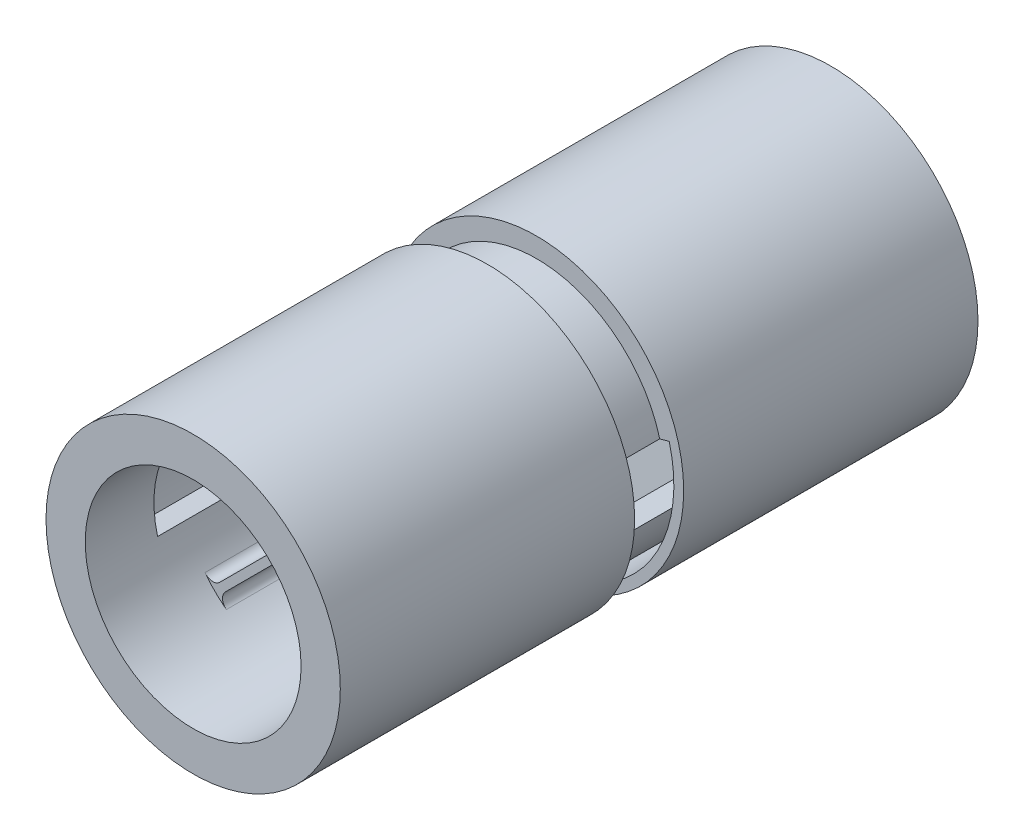
SolidWorks part; units mm, degrees
material "AISI 316 Stainless Steel Sheet (SS)"
ref_plane "Front Plane" through (0, 0, 0) normal (0, 0, 1) x (1, 0, 0)
ref_plane "Top Plane" through (0, 0, 0) normal (0, 1, 0) x (1, 0, 0)
ref_plane "Right Plane" through (0, 0, 0) normal (1, 0, 0) x (0, 0, -1)
sketch "Sketch1" plane through (0, 0, 0) normal (0, 0, 1) x (1, 0, 0)
  line L0 (-10.6252, -2.847) -> (-13.523, -3.6235)
  line L1 (0, 0) -> (-15, 0) construction
  line L2 (0, 0) -> (0, -15) construction
  line L3 (10.6252, -2.847) -> (13.523, -3.6235)
  line L4 (-13.523, -3.6235) -> (0, 0) construction
  line L5 (13.523, -3.6235) -> (0, 0) construction
  circle A0 centre (0, 0) radius 15
  arc A1 (13.523, -3.6235) -> (-13.523, -3.6235) centre (0, 0) ccw
  arc A2 (-10.6252, -2.847) -> (10.6252, -2.847) centre (0, 0) ccw
  dimension "D1" = 30
  dimension "D2" = 28
  dimension "D3" = 22
  dimension "D4" = 15
extrude "Boss-Extrude1" add sketch "Sketch1" along normal blind 45
sketch "Sketch2" plane through (0, 0, 0) normal (0, 0, -1) x (-1, 0, 0)
  circle A0 centre (0, 0) radius 15
  circle A1 centre (0, 0) radius 15 construction
  circle A2 centre (0, 0) radius 13
  dimension "D1" = 26
extrude "Cut-Extrude1" cut sketch "Sketch2" against normal blind 25
ref_axis "Axis1" through (0, 0, 45) along (0, 0, -1)
ref_plane "Plane1" through (0, 0, 22.5) normal (0, 0, 1) x (1, 0, 0)
sketch "Sketch5" plane through (0, 0, 45) normal (0, 0, 1) x (1, 0, 0)
  line L0 (0, 0) -> (0, -11) construction
  line L1 (0, 0) -> (-10.6066, -10.6066) construction
  line L2 (-7.4953, -8.061) -> (8.061, 7.4953)
  line L3 (-7.4953, -8.061) -> (-8.061, -7.4953)
  line L4 (0, 0) -> (0.2828, -0.2828) construction
  line L5 (-8.061, -7.4953) -> (7.4953, 8.061)
  line L6 (8.061, 7.4953) -> (7.4953, 8.061)
  arc A0 (-10.6252, -2.847) -> (10.6252, -2.847) centre (0, 0) ccw construction
  circle A1 centre (0, 0) radius 15 construction
  point P14 (-7.7782, -7.7782)
  point P15 (-0.2828, 0.2828)
  dimension "D1" = 45
  dimension "D2" = 0.4
extrude "Boss-Extrude4" add sketch "Sketch5" against normal blind 10
mirror "Mirror1" about plane through (0, 0, 22.5) normal (0, 0, 1) of "Boss-Extrude4"
sketch "Sketch6" plane through (0, 0, 0) normal (0, 0, -1) x (-1, 0, 0)
  line L0 (10.6252, 2.847) -> (13.523, 3.6235)
  line L1 (0, 0) -> (15, 0) construction
  line L2 (0, 0) -> (0, 15) construction
  line L3 (-10.6252, 2.847) -> (-13.523, 3.6235)
  line L4 (0, 0) -> (-10.6252, 2.847) construction
  line L5 (0, 0) -> (10.6252, 2.847) construction
  circle A0 centre (0, 0) radius 15
  arc A1 (10.6252, 2.847) -> (-10.6252, 2.847) centre (0, 0) ccw
  circle A2 centre (0, 0) radius 15 construction
  arc A3 (8.0559, -7.4902) -> (10.6252, -2.847) centre (0, 0) ccw construction
  arc A4 (13.523, 3.6235) -> (-13.523, 3.6235) centre (0, 0) cw
  dimension "D2" = 14
  dimension "D1" = 15
  dimension "D3" = 165
extrude "Boss-Extrude5" add sketch "Sketch6" against normal blind 20
sketch "Sketch7" plane through (0, 0, 0) normal (0, 0, -1) x (-1, 0, 0)
  line L0 (13.523, 3.6235) -> (10.6252, 2.847) construction
  line L1 (-10.6252, 2.847) -> (-13.523, 3.6235) construction
  line L2 (-12.557, 3.3646) -> (-10.6252, 2.847)
  line L3 (12.557, 3.3646) -> (10.6252, 2.847)
  arc A0 (12.557, 3.3646) -> (-12.557, 3.3646) centre (0, 0) ccw
  arc A1 (10.6252, 2.847) -> (-10.6252, 2.847) centre (0, 0) ccw
  arc A2 (-12.557, -3.3646) -> (12.557, -3.3646) centre (0, 0) ccw construction
extrude "Boss-Extrude6" add sketch "Sketch7" against normal up to surface (45 mm away) up to face at (0.1498, -0.0731, 45)
sketch "Sketch8" plane through (0, 0, 22.5) normal (0, 0, 1) x (1, 0, 0)
  line L0 (0, 0) -> (9.8995, -9.8995) construction
  line L1 (-7.4902, -8.0559) -> (8.0559, 7.4902) construction
  line L2 (8.061, -7.4953) -> (7.4953, -8.061)
  line L3 (7.4953, -8.061) -> (-8.061, 7.4953)
  line L4 (0, 0) -> (-0.2828, -0.2828) construction
  line L5 (8.061, -7.4953) -> (-7.4953, 8.061)
  line L6 (-7.4953, 8.061) -> (-8.061, 7.4953)
  arc A0 (-13.523, 3.6235) -> (13.523, 3.6235) centre (0, 0) ccw construction
  point P13 (7.7782, -7.7782)
  point P14 (0.2828, 0.2828)
  dimension "D1" = 11
  dimension "D2" = 0.4
extrude "Boss-Extrude7" add sketch "Sketch8" against normal offset from surface 1 and the other way offset from surface 1 up to face at (0, 0, 10) other way up to face at (0, 0, 35)
fillet "Fillet1" radius 1 12 edges at (7.4902, 8.0559, 5) (7.4902, 8.0559, 40) (8.0559, 7.4902, 40) (8.0559, 7.4902, 5) (-8.0559, 7.4902, 22.5) (-7.4902, 8.0559, 22.5) (-7.4902, -8.0559, 40) (-7.4902, -8.0559, 5) (-8.0559, -7.4902, 40) (-8.0559, -7.4902, 5) (8.0559, -7.4902, 22.5) (7.4902, -8.0559, 22.5)
sketch "Sketch9" plane through (0, 0, 45) normal (0, 0, 1) x (1, 0, 0)
  line L0 (13.523, -3.6235) -> (10.6252, -2.847)
  line L1 (-10.6252, -2.847) -> (-13.523, -3.6235)
  circle A0 centre (0, 0) radius 15
  arc A1 (13.523, -3.6235) -> (-13.523, -3.6235) centre (0, 0) ccw
  circle A2 centre (0, 0) radius 15 construction
  arc A3 (13.523, -3.6235) -> (-13.523, -3.6235) centre (0, 0) ccw construction
  arc A4 (-10.6252, -2.847) -> (10.6252, -2.847) centre (0, 0) ccw
  arc A5 (-6.6126, -8.7905) -> (10.6252, -2.847) centre (0, 0) ccw construction
extrude "Boss-Extrude8" add sketch "Sketch9" along normal blind 10
sketch "Sketch10" plane through (0, 0, 55) normal (0, 0, 1) x (1, 0, 0)
  line L0 (-13.523, -3.6235) -> (-10.6252, -2.847)
  line L1 (13.523, -3.6235) -> (10.6252, -2.847)
  arc A0 (10.6252, -2.847) -> (-10.6252, -2.847) centre (0, 0) ccw
  arc A1 (13.523, -3.6235) -> (-13.523, -3.6235) centre (0, 0) ccw
  arc A2 (-10.6252, -2.847) -> (10.6252, -2.847) centre (0, 0) ccw construction
  arc A3 (13.523, -3.6235) -> (-13.523, -3.6235) centre (0, 0) ccw construction
extrude "Boss-Extrude9" add sketch "Sketch10" against normal offset from surface (7 mm away) 3 up to face at (-0.1095, 2.2815, 45)
sketch "Sketch11" plane through (0, 0, 0) normal (0, 0, -1) x (-1, 0, 0)
  line L0 (10.6252, 2.847) -> (13.523, 3.6235)
  line L1 (-10.6252, 2.847) -> (-13.523, 3.6235)
  arc A0 (10.6252, 2.847) -> (-10.6252, 2.847) centre (0, 0) ccw
  circle A1 centre (0, 0) radius 15
  arc A2 (10.6252, 2.847) -> (-6.6126, 8.7905) centre (0, 0) ccw construction
  circle A3 centre (0, 0) radius 15 construction
  arc A4 (-13.523, 3.6235) -> (13.523, 3.6235) centre (0, 0) ccw
  arc A5 (-13.523, 3.6235) -> (13.523, 3.6235) centre (0, 0) ccw construction
extrude "Boss-Extrude10" add sketch "Sketch11" along normal blind 10
sketch "Sketch12" plane through (0, 0, -10) normal (0, 0, -1) x (-1, 0, 0)
  line L0 (13.523, 3.6235) -> (10.6252, 2.847)
  line L1 (-10.6252, 2.847) -> (-13.523, 3.6235)
  line L2 (-10.6252, 2.847) -> (-13.523, 3.6235) construction
  arc A0 (-10.6252, 2.847) -> (10.6252, 2.847) centre (0, 0) ccw
  arc A1 (-13.523, 3.6235) -> (13.523, 3.6235) centre (0, 0) ccw
  arc A2 (10.6252, 2.847) -> (-10.6252, 2.847) centre (0, 0) ccw construction
  arc A3 (-13.523, 3.6235) -> (13.523, 3.6235) centre (0, 0) ccw construction
extrude "Boss-Extrude11" add sketch "Sketch12" against normal offset from surface (7 mm away) 3 up to face at (0.0623, -2.2343, 0)
